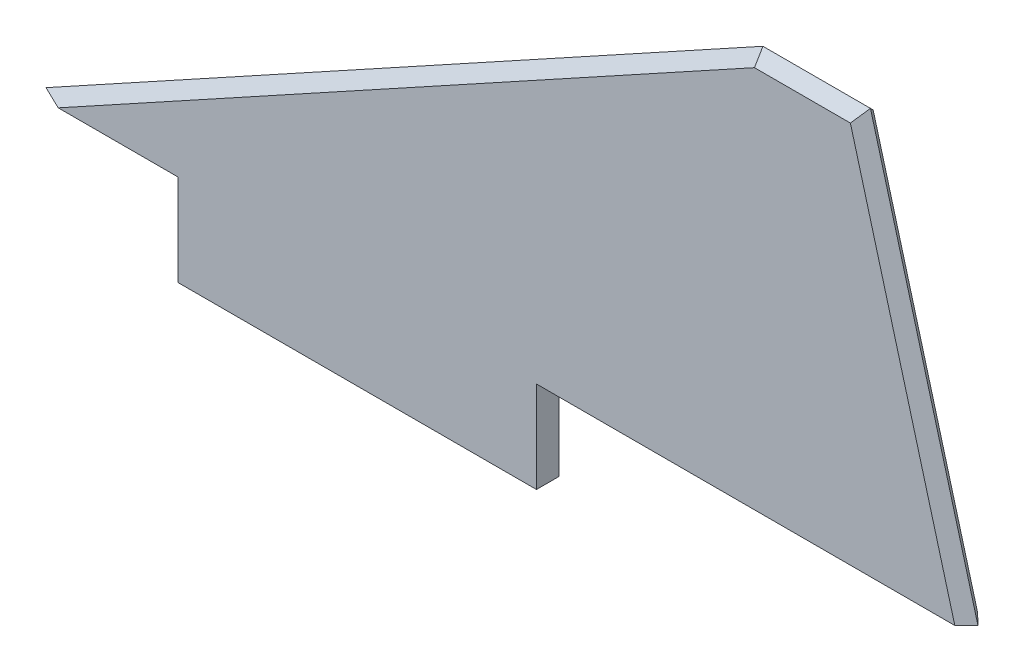
SolidWorks part; units mm, degrees
ref_plane "Front Plane" through (0, 0, 0) normal (0, 0, 1) x (1, 0, 0)
ref_plane "Top Plane" through (0, 0, 0) normal (0, 1, 0) x (1, 0, 0)
ref_plane "Right Plane" through (0, 0, 0) normal (1, 0, 0) x (0, 0, -1)
sketch "Sketch1" plane through (0, 0, 0) normal (0, 0, 1) x (1, 0, 0)
  line L0 (0, 0) -> (20, 0)
  line L1 (20, 0) -> (20, -12.75)
  line L2 (20, -12.75) -> (70, -12.75)
  line L3 (70, -12.75) -> (70, 0)
  line L4 (70, 0) -> (130, 0)
  line L5 (130, 0) -> (115, 55)
  line L6 (115, 55) -> (100, 55)
  line L7 (100, 55) -> (0, 0)
  dimension "D1" = 20
  dimension "D2" = 12.75
  dimension "D3" = 50
  dimension "D4" = 60
  dimension "D5" = 15
  dimension "D6" = 15
  dimension "D7" = 55
extrude "Boss-Extrude1" add sketch "Sketch1" along normal blind 3.175
chamfer "Chamfer1" distance 1.5875 angle 45 6 edges at (50, 27.5, 3.175) (107.5, 55, 3.175) (122.5, 27.5, 3.175) (50, 27.5, 0) (107.5, 55, 0) (122.5, 27.5, 0)
